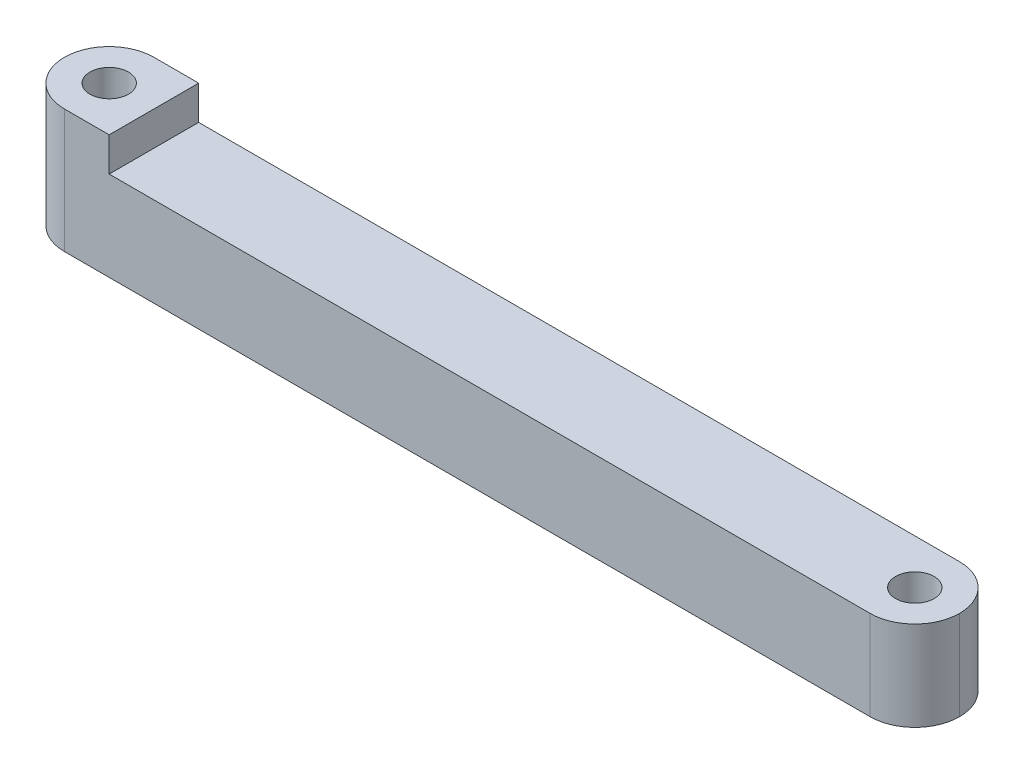
SolidWorks part; units mm, degrees
ref_plane "정면" through (0, 0, 0) normal (0, 0, 1) x (1, 0, 0)
ref_plane "윗면" through (0, 0, 0) normal (0, 1, 0) x (1, 0, 0)
ref_plane "우측면" through (0, 0, 0) normal (1, 0, 0) x (0, 0, -1)
sketch "스케치1" plane through (0, 0, 0) normal (0, 0, 1) x (1, 0, 0)
  line L1 (-50, -5) -> (50, -5)
  line L2 (-50, -5) -> (-50, 5)
  line L3 (-50, 5) -> (50, 5)
  line L4 (50, -5) -> (50, 5)
  line L5 (-50, -5) -> (50, 5) construction
  line L6 (-50, 5) -> (50, -5) construction
  point P0 (0, 0)
  dimension "D1" = 100
  dimension "D2" = 10
extrude "보스-돌출1" add sketch "스케치1" along normal blind 10
sketch "스케치4" plane through (0, 5, 0) normal (0, 1, 0) x (1, 0, 0)
  line L0 (50, 0) -> (-50, 0) construction
  line L1 (-40, 0) -> (-50, 0)
  line L2 (-40, 0) -> (-40, -10)
  line L3 (-40, -10) -> (-50, -10)
  line L4 (-50, 0) -> (-50, -10)
  dimension "D1" = 10
extrude "보스-돌출2" add sketch "스케치4" along normal blind 3.8
fillet "필렛1" radius 5 4 edges at (50, 0, 10) (50, 0, 0) (-50, 1.9, 0) (-50, 1.9, 10)
sketch "스케치2" plane through (0, 8.8, 0) normal (0, 1, 0) x (1, 0, 0)
  circle A0 centre (-45, -5) radius 2.15
  circle A1 centre (45, -5) radius 2.15
  dimension "D1" = 4.3
  dimension "D2" = 4.3
extrude "컷-돌출1" cut sketch "스케치2" against normal through all
